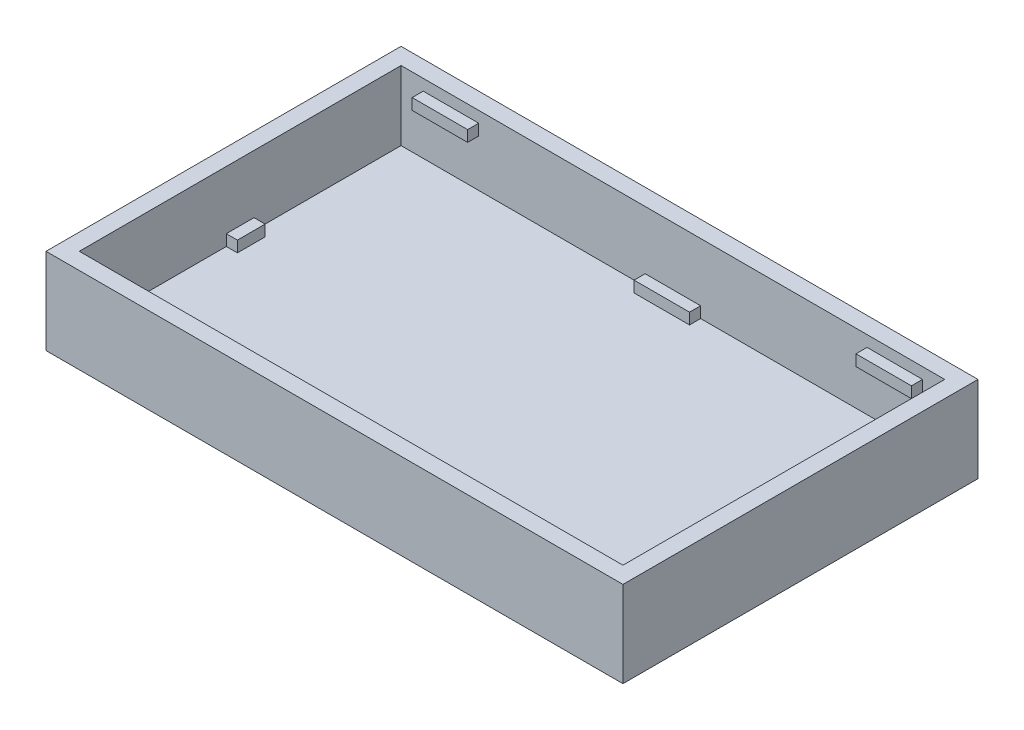
SolidWorks part; units mm, degrees
ref_plane "前视基准面" through (0, 0, 0) normal (0, 0, 1) x (1, 0, 0)
ref_plane "上视基准面" through (0, 0, 0) normal (0, 1, 0) x (1, 0, 0)
ref_plane "右视基准面" through (0, 0, 0) normal (1, 0, 0) x (0, 0, -1)
other "Configuration Table"
sketch "草图1" plane through (0, 0, 0) normal (0, 1, 0) x (1, 0, 0)
  line L1 (-42, -25) -> (42, -25)
  line L2 (-45, -22) -> (-45, 22)
  line L3 (-42, 25) -> (42, 25)
  line L4 (45, -22) -> (45, 22)
  line L5 (-45, -25) -> (45, 25) construction
  line L6 (-45, 25) -> (45, -25) construction
  line L7 (-49, 29) -> (49, 29)
  line L8 (-49, 29) -> (-49, -29)
  line L9 (-49, -29) -> (49, -29)
  line L10 (49, 29) -> (49, -29)
  line L11 (-52, 32) -> (52, 32)
  line L12 (-52, 32) -> (-52, -32)
  line L13 (-52, -32) -> (52, -32)
  line L14 (52, 32) -> (52, -32)
  arc A0 (-42, -25) -> (-45, -22) centre (-42, -22) cw
  arc A1 (45, -22) -> (42, -25) centre (42, -22) cw
  arc A2 (45, 22) -> (42, 25) centre (42, 22) ccw
  arc A3 (-45, 22) -> (-42, 25) centre (-42, 22) cw
  circle A4 centre (-39, 19) radius 1.5
  circle A5 centre (39, 19) radius 1.5
  circle A6 centre (-39, -19) radius 1.5
  circle A7 centre (39, -19) radius 1.5
  point P0 (0, 0)
  dimension "D3" = 3
  dimension "D4" = 3
  dimension "D1" = 90
  dimension "D2" = 50
  dimension "D5" = 6
  dimension "D6" = 6
  dimension "D7" = 6
  dimension "D8" = 6
  dimension "D9" = 4
  dimension "D10" = 4
  dimension "D11" = 4
  dimension "D12" = 4
  dimension "D13" = 3
  dimension "D14" = 3
  dimension "D15" = 3
  dimension "D16" = 3
extrude "凸台-拉伸1" add sketch "草图1" along normal blind 2 contours L12 L13 L14 L11 | L8 L9 L10 L7
extrude "凸台-拉伸2" add sketch "草图1<3>" against normal blind 3 contours L13 L14 L11 L12
sketch "草图1<3>" plane through (0, 0, 0) normal (0, 1, 0) x (1, 0, 0) same geometry as "草图1"
sketch "草图2" plane through (0, 0, 0) normal (0, 1, 0) x (1, 0, 0)
  line L0 (-49, 29) -> (-49, -29) construction
  line L1 (-49, 2.5) -> (-47, 2.5)
  line L2 (-49, 2.5) -> (-49, -2.5)
  line L3 (-49, -2.5) -> (-47, -2.5)
  line L4 (-47, 2.5) -> (-47, -2.5)
  line L5 (49, 29) -> (49, -29) construction
  line L6 (49, 2.5) -> (47, 2.5)
  line L7 (49, 2.5) -> (49, -2.5)
  line L8 (49, -2.5) -> (47, -2.5)
  line L9 (47, 2.5) -> (47, -2.5)
  line L10 (-49, 29) -> (49, 29) construction
  line L11 (-5, 29) -> (5, 29)
  line L12 (-5, 29) -> (-5, 27)
  line L13 (-5, 27) -> (5, 27)
  line L14 (5, 29) -> (5, 27)
  line L15 (-49, -29) -> (49, -29) construction
  line L16 (-5, -29) -> (5, -29)
  line L17 (-5, -29) -> (-5, -27)
  line L18 (-5, -27) -> (5, -27)
  line L19 (5, -29) -> (5, -27)
  line L20 (-47, 0) -> (47, 0)
  line L21 (0, 27) -> (0, -27)
  dimension "D1" = 2
  dimension "D2" = 5
  dimension "D3" = 10
extrude "凸台-拉伸3" add sketch "草图2" along normal up to surface (2 mm away) contours L3 L4 L1 L2 | L13 L14 L11 L12 | L16 L19 L18 L17 | L8 L9 L6 L7 up to face at (0, 2, 0)
extrude "凸台-拉伸4" add sketch "草图1<4>" along normal blind 8.5 from surface contours L13 L14 L11 L12 | L8 L9 L10 L7 starting at face at (0, 2, 0)
sketch "草图1<4>" plane through (0, 0, 0) normal (0, 1, 0) x (1, 0, 0) same geometry as "草图1"
sketch "草图3" plane through (0, 10.5, 0) normal (0, 1, 0) x (1, 0, 0)
  line L0 (-49, -29) -> (49, -29) construction
  line L1 (45, -29) -> (35, -29)
  line L2 (45, -29) -> (45, -27)
  line L3 (45, -27) -> (35, -27)
  line L4 (35, -29) -> (35, -27)
  line L5 (-49, 29) -> (49, 29) construction
  line L6 (-45, -29) -> (-35, -29)
  line L7 (-45, -29) -> (-45, -27)
  line L8 (-45, -27) -> (-35, -27)
  line L9 (-35, -29) -> (-35, -27)
  line L10 (45, 29) -> (35, 29)
  line L11 (45, 29) -> (45, 27)
  line L12 (45, 27) -> (35, 27)
  line L13 (35, 29) -> (35, 27)
  line L14 (-49, 29) -> (-49, -29) construction
  line L15 (-35, 29) -> (-45, 29)
  line L16 (-35, 29) -> (-35, 27)
  line L17 (-35, 27) -> (-45, 27)
  line L18 (-45, 29) -> (-45, 27)
  line L19 (49, 29) -> (49, -29) construction
  dimension "D1" = 4
  dimension "D2" = 4
  dimension "D3" = 2
  dimension "D4" = 2
  dimension "D5" = 10
extrude "凸台-拉伸5" add sketch "草图3" against normal blind 2
extrude "凸台-拉伸6" add sketch "草图1<5>" along normal blind 2 from surface contours L14 L13 L12 L11 | L9 L10 L7 L8 starting at face at (0, 10.5, 0)
sketch "草图1<5>" plane through (0, 0, 0) normal (0, 1, 0) x (1, 0, 0) same geometry as "草图1"
